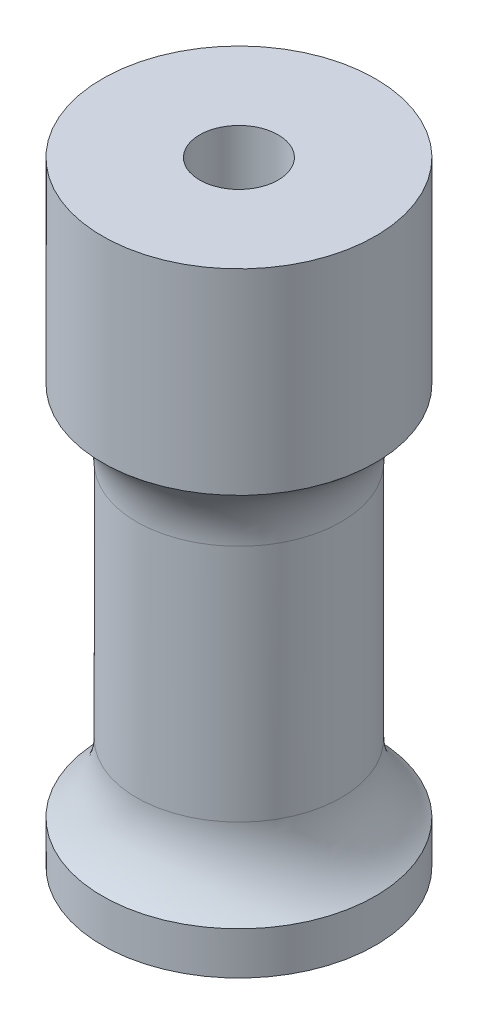
SolidWorks part; units mm, degrees
ref_plane "Спереди" through (0, 0, 0) normal (0, 0, 1) x (1, 0, 0)
ref_plane "Сверху" through (0, 0, 0) normal (0, 1, 0) x (1, 0, 0)
ref_plane "Справа" through (0, 0, 0) normal (1, 0, 0) x (0, 0, -1)
sketch "Эскиз1" plane through (0, 0, 0) normal (0, 0, 1) x (1, 0, 0)
  line L0 (0, 0) -> (2.3, 0) construction
  line L1 (2.3, 0) -> (2.3, 36)
  line L2 (2.3, 36) -> (7.5, 36)
  line L8 (6, 0) -> (2.3, 0)
  line L9 (0, 0) -> (0, 9.2687) construction
  line L10 (6, 0) -> (8, 0)
  line L11 (8, 0) -> (8, 2.5)
  line L12 (8, 2.5) -> (6, 2.5)
  line L13 (6, 2.5) -> (6, 24.5)
  line L14 (6, 24.5) -> (8, 24.5)
  line L15 (8, 24.5) -> (8, 36)
  line L16 (8, 36) -> (7.5, 36)
  line L17 (6, 0) -> (6, 2.5) construction
  dimension "D1" = 2.3
  dimension "D2" = 6
  dimension "D3" = 2
  dimension "D4" = 2.5
  dimension "D5" = 36
  dimension "D6" = 11.5
revolve "Повернуть1" add sketch "Эскиз1" angle 360 about L9
fillet "Скругление1" radius 5 2 edges at (0, 24.5, -6) (0, 2.5, -6)
